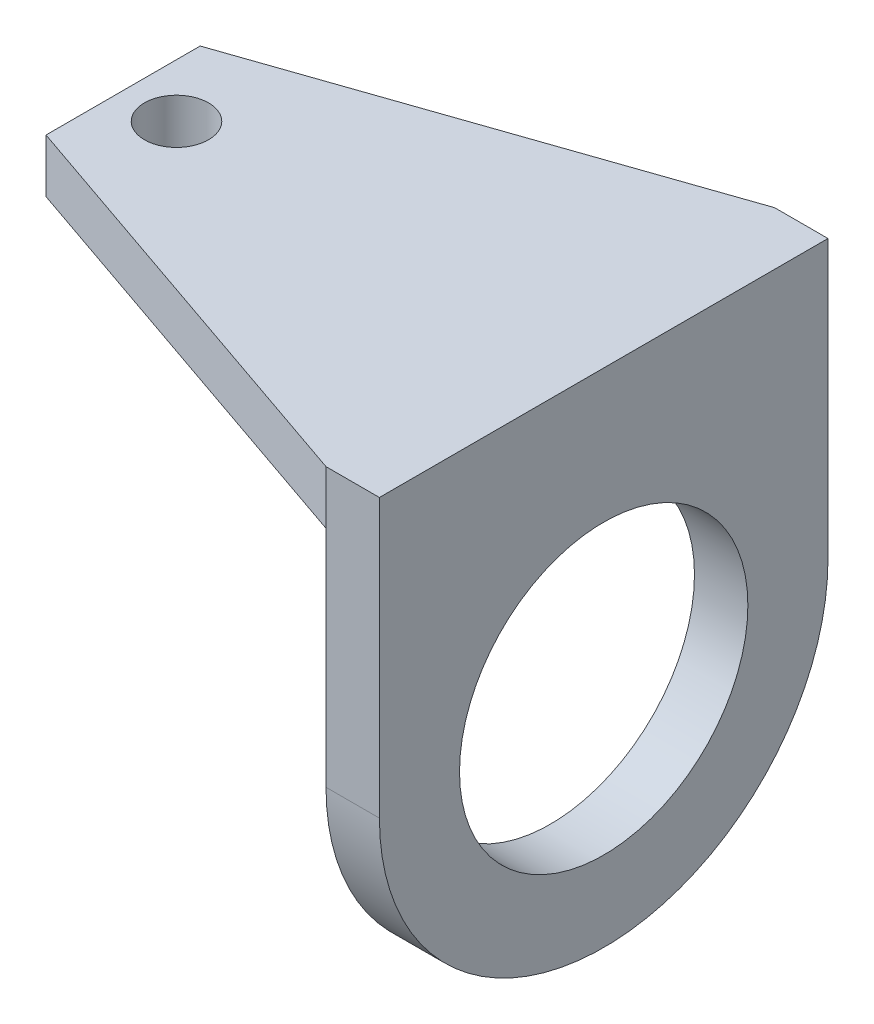
SolidWorks part; units mm, degrees
ref_plane "Front Plane" through (0, 0, 0) normal (0, 0, 1) x (1, 0, 0)
ref_plane "Top Plane" through (0, 0, 0) normal (0, 1, 0) x (1, 0, 0)
ref_plane "Right Plane" through (0, 0, 0) normal (1, 0, 0) x (0, 0, -1)
sketch "Sketch1" plane through (0, 0, 0) normal (1, 0, 0) x (0, 0, -1)
  circle A0 centre (0, 0) radius 13.5
  circle A1 centre (0, 0) radius 21
  dimension "D1" = 27
  dimension "D2" = 7.5
extrude "Boss-Extrude1" add sketch "Sketch1" along normal blind 5
ref_plane "Plane1" through (0, 21, 0) normal (0, 1, 0) x (1, 0, 0)
sketch "Sketch2" plane through (0, 21, 0) normal (0, 1, 0) x (1, 0, 0)
  line L0 (5, -21) -> (5, 21) construction
  line L1 (5, -21) -> (5, 21)
  line L2 (0, 21) -> (0, -21) construction
  line L3 (0, 21) -> (0, -21)
  line L4 (5, -21) -> (-40, -21)
  line L5 (-40, -21) -> (-40, 21)
  line L6 (-40, 21) -> (5, 21)
  line L7 (-35, 0) -> (-42.2528, 0) construction
  circle A1 centre (-35, 0) radius 3
  dimension "D2" = 6
  dimension "D4" = 2
  dimension "D1" = 45
extrude "Boss-Extrude2" add sketch "Sketch2" against normal up to surface (21 mm away) contours L6 L3 L4 L1 region at (2.5, 21, 0) up to face at (5, 0, -21)
extrude "Boss-Extrude3" add sketch "Sketch2<3>" along normal blind 5 contours L6 L5 L4 L3 | L6 L3 L4 L1 | A1 L5 L4 | A1 L6 L5 | L6 | L4 region at (2.5, 21, 0) region at (-19.7432, 21, 0)
sketch "Sketch2<3>" plane through (0, 21, 0) normal (0, 1, 0) x (1, 0, 0) same geometry as "Sketch2"
ref_point "Point1"
sketch "Sketch3" plane through (0, 21, 0) normal (0, -1, 0) x (1, 0, 0)
  line L0 (0, -21) -> (-40, -7.216)
  line L1 (-40, 21) -> (-40, -21) construction
  line L2 (-40, -7.216) -> (-40, 7.216)
  line L3 (-35, 0) -> (-42.2327, 0) construction
  line L4 (0, -21) -> (0, 21) construction
  line L5 (0, -21) -> (0, 21)
  line L6 (0, 21) -> (-40, 7.216)
  line L7 (0, -21) -> (0, -28.4718)
  line L8 (0, -28.4718) -> (-40, -28.4718)
  line L9 (-40, -28.4718) -> (-40, 27.2513)
  line L10 (-40, 27.2513) -> (0, 27.2513)
  line L11 (0, 27.2513) -> (0, 21)
  point P12 (-40, 0)
  line M7 (-40, -21) -> (0, -21)
  line M9 (0, 21) -> (-40, 21)
  line M10 (-40, 21) -> (-40, -21)
extrude "Cut-Extrude4" cut sketch "Sketch3" against normal through all contours L2 L3 L9 L8 L7 M7 M10 | L3 L11 L10 L9 M10 M9 | L0 M7 M10 | L6 M9 M10 region at (-26.6667, 21, -16.4053) region at (-20, 21, -24.7359) region at (-20, 21, 24.1256) region at (-26.6667, 21, 16.4053)
